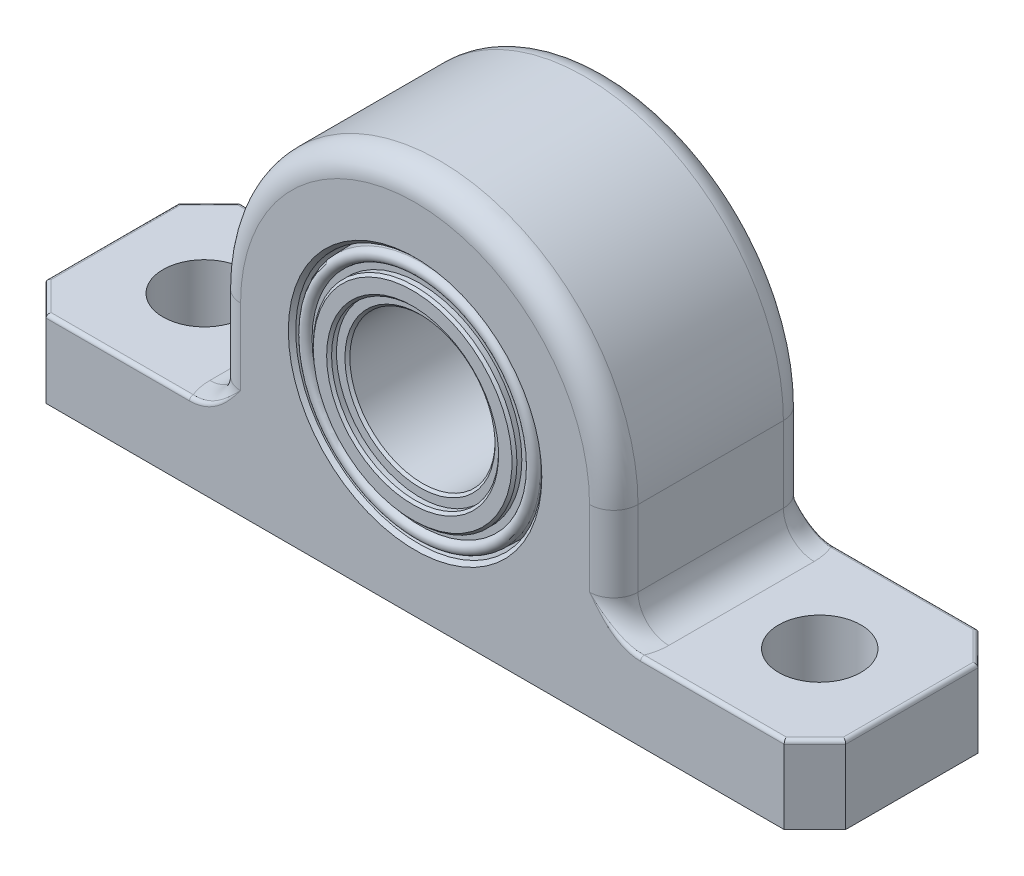
SolidWorks part; units mm, degrees
material "1060 Alloy"
ref_plane "Front Plane" through (0, 0, 0) normal (0, 0, 1) x (1, 0, 0)
ref_plane "Top Plane" through (0, 0, 0) normal (0, 1, 0) x (1, 0, 0)
ref_plane "Right Plane" through (0, 0, 0) normal (1, 0, 0) x (0, 0, -1)
sketch "Sketch1" plane through (0, 0, 0) normal (0, 0, 1) x (1, 0, 0)
  line L0 (-41.25, 0) -> (41.25, 0)
  line L1 (41.25, 0) -> (41.25, 8)
  line L2 (-41.25, 0) -> (-41.25, 8)
  line L3 (-41.25, 8) -> (-20.5, 8)
  line L4 (41.25, 8) -> (20.5, 8)
  line L5 (-20.5, 8) -> (-20.5, 19)
  line L6 (20.5, 8) -> (20.5, 19)
  line L7 (0, 0) -> (0, 39.5) construction
  line L8 (5.2976, 24.2976) -> (14.4957, 33.4957) construction
  circle A0 centre (0, 19) radius 7.492
  arc A1 (20.5, 19) -> (-20.5, 19) centre (0, 19) ccw
  circle A2 centre (0, 19) radius 12.6952 construction
  point P16 (8.9769, 27.9769)
  point P17 (0, 26.492)
  point P18 (0, 31.6952)
  dimension "D1" = 45
  dimension "D2" = 13.008
  dimension "D3" = 5.2032
sketch "Sketch2" plane through (0, 0, 0) normal (0, 1, 0) x (1, 0, 0)
  line L0 (-31.75, 0) -> (31.75, 0) construction
  line L1 (-41.25, -10) -> (41.25, 10) construction
  line L2 (-41.25, 10) -> (41.25, 10)
  line L3 (-41.25, 10) -> (-41.25, -10)
  line L4 (-41.25, -10) -> (41.25, -10)
  line L5 (41.25, 10) -> (41.25, -10)
  circle A0 centre (-31.75, 0) radius 4.25
  circle A1 centre (31.75, 0) radius 4.25
sketch "Sketch3" plane through (0, 0, 0) normal (0, 0, 1) x (1, 0, 0)
  line L0 (-41.25, 0) -> (-41.25, 8) construction
  line L1 (-41.25, 0) -> (41.25, 0) construction
  line L2 (-41.25, 8) -> (-20.5, 8) construction
  line L3 (41.25, 8) -> (20.5, 8) construction
  line L4 (41.25, 0) -> (41.25, 8) construction
  line L5 (20.5, 8) -> (20.5, 19) construction
  line L6 (-20.5, 8) -> (-20.5, 19) construction
  line L7 (-41.25, 0) -> (-41.25, 8)
  line L8 (-41.25, 0) -> (41.25, 0)
  line L9 (-41.25, 8) -> (-20.5, 8)
  line L10 (41.25, 8) -> (20.5, 8)
  line L11 (41.25, 0) -> (41.25, 8)
  line L12 (20.5, 8) -> (20.5, 19)
  line L13 (-20.5, 8) -> (-20.5, 19)
  arc A0 (20.5, 19) -> (-20.5, 19) centre (0, 19) ccw construction
  circle A1 centre (0, 19) radius 12.6952 construction
  arc A2 (20.5, 19) -> (-20.5, 19) centre (0, 19) ccw
  circle A3 centre (0, 19) radius 12.6952
extrude "Boss-Extrude1" add sketch "Sketch3" against normal up to vertex (10 mm away) and the other way up to vertex (10 mm away) up to point (-41.25, 0, -10) other way up to point (-41.25, 0, 10)
sketch "Sketch4" plane through (0, 0, 0) normal (0, 1, 0) x (1, 0, 0)
  circle A0 centre (-31.75, 0) radius 4.25 construction
  circle A1 centre (31.75, 0) radius 4.25 construction
  circle A2 centre (-31.75, 0) radius 4.25
  circle A3 centre (31.75, 0) radius 4.25
extrude "Cut-Extrude1" cut sketch "Sketch4" along normal through all
chamfer "Chamfer1" distance 3.175 angle 45 4 edges at (-41.25, 4, -10) (41.25, 4, 10) (41.25, 4, -10) (-41.25, 4, 10)
fillet "Fillet1" radius 2.5 6 edges at (-20.5, 13.5, -10) (0, 39.5, -10) (-20.5, 13.5, 10) (0, 39.5, 10) (20.5, 13.5, -10) (20.5, 13.5, 10)
fillet "Fillet2" radius 3.175 6 edges at (-19.7678, 8, -9.2678) (-19.7678, 8, 9.2678) (19.7678, 8, -9.2678) (19.7678, 8, 9.2678) (-20.5, 8, 0) (20.5, 8, 0)
chamfer "Chamfer2" distance 0.381 angle 45 2 edges at (12.6952, 19, 10) (12.6952, 19, -10)
fillet "Fillet3" radius 0.381 14 edges at (-21.6759, 8.2477, -10) (-21.6759, 8.2477, 10) (21.6759, 8.2477, -10) (21.6759, 8.2477, 10) (-30.5848, 8, -10) (-39.6625, 8, -8.4125) (-41.25, 8, 0) (-39.6625, 8, 8.4125) (-30.5848, 8, 10) (30.5848, 8, -10) (39.6625, 8, -8.4125) (41.25, 8, 0) (39.6625, 8, 8.4125) (30.5848, 8, 10)
sketch "Sketch5" plane through (0, 0, 0) normal (1, 0, 0) x (0, 0, -1)
  line L1 (-10, 31.6952) -> (10, 31.6952)
  line L2 (-10, 31.6952) -> (-10, 26.492)
  line L3 (-10, 26.492) -> (10, 26.492)
  line L4 (10, 31.6952) -> (10, 26.492)
sketch "Sketch6" plane through (0, 0, 0) normal (1, 0, 0) x (0, 0, -1)
  line L0 (0, 31.6952) -> (10, 31.6952)
  line L1 (-10, 31.6952) -> (10, 31.6952) construction
  line L2 (0, 31.6952) -> (-9.4014, 31.3669)
  line L3 (-10, 31.6952) -> (-10, 26.492) construction
  line L4 (-9.492, 30.137) -> (-9.492, 29.5079)
  line L5 (-9.492, 29.5079) -> (-10.254, 29.5079)
  line L6 (-10.254, 29.5079) -> (-10.254, 27.6158)
  line L7 (-10.254, 27.6158) -> (-9.492, 27.6158)
  line L8 (-9.492, 27.6158) -> (-9.492, 26.492)
  line L9 (-10, 26.492) -> (10, 26.492) construction
  line L10 (-9.492, 26.492) -> (7.968, 26.492)
  line L11 (10, 31.6952) -> (10, 30.137)
  line L12 (10, 31.6952) -> (10, 26.492) construction
  line L13 (10, 30.137) -> (6.19, 30.137)
  line L14 (6.19, 30.137) -> (6.19, 29.5079)
  line L15 (6.19, 29.5079) -> (8.73, 29.5079)
  line L16 (8.73, 29.5079) -> (8.73, 27.6158)
  line L17 (8.73, 27.6158) -> (7.968, 27.6158)
  line L18 (7.968, 27.6158) -> (7.968, 26.492)
  line L20 (-10, 19) -> (10, 19) construction
  line L21 (-10, 0) -> (-10, 7.619) construction
  arc A0 (-9.4014, 31.3669) -> (-9.492, 30.137) centre (-9.3798, 30.747) ccw
  dimension "D3" = 0.762
  dimension "D4" = 5.2032
  dimension "D5" = 1.27
  dimension "D6" = 2.54
  dimension "D7" = 1.8921
  dimension "D8" = 1.2298
  dimension "D9" = 17.2316
revolve "Revolve1" add sketch "Sketch6" angle 360 about L20
chamfer "Chamfer3" distance 0.254 angle 45 6 edges at (8.6158, 19, -8.73) (10.5079, 19, -8.73) (7.492, 19, 9.492) (7.492, 19, -7.968) (10.5079, 19, 10.254) (8.6158, 19, 10.254)
ref_axis "Center Axis 1" through (0, 19, -7.714) along (0, 0, 1)
ref_plane "Contact Plane 1" through (0, 0, 0) normal (0, -1, 0) x (-1, 0, 0)
equation "\"D3@Sketch1\"=\"D2@Sketch1\"/2.50"
equation "\"D1@Fillet1\"=\"Overall Width@Sketch2\"/8"
equation "\"D7@Sketch6\"=\"D4@Sketch6\"/2.750"
equation "\"D8@Sketch6\"=\"D7@Sketch6\"*.65"
equation "\"D9@Sketch6\"=\"ID@Sketch1\"*1.15"
